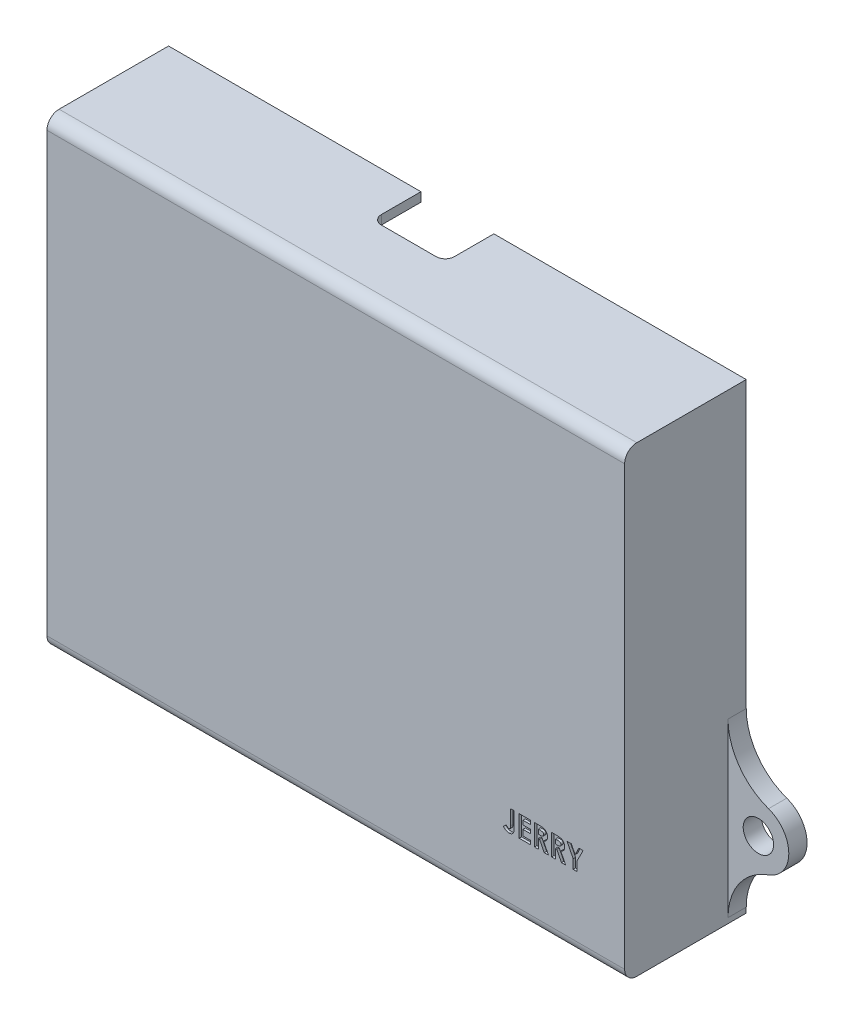
SolidWorks part; units mm, degrees
ref_plane "Front Plane" through (0, 0, 0) normal (0, 0, 1) x (1, 0, 0)
ref_plane "Top Plane" through (0, 0, 0) normal (0, 1, 0) x (1, 0, 0)
ref_plane "Right Plane" through (0, 0, 0) normal (1, 0, 0) x (0, 0, -1)
ref_plane "Plane1" through (-67.462, 80, -13) normal (1, 0, 0) x (0, 0, -1)
sketch "Sketch3" plane through (0, 0, 0) normal (0, 0, 1) x (1, 0, 0)
  line L0 (-47.5, 86) -> (-38, 86) construction
  line L1 (-47.5, 10) -> (-47.5, 10.8579) construction
  line L2 (-47.5, 10) -> (-38, 10) construction
  line L3 (-47.5, 39.1421) -> (-47.5, 86) construction
  line L4 (-47.5, 86) -> (47.5, 86)
  line L5 (-47.5, 10) -> (-47.5, 10.8579)
  line L6 (-47.5, 10) -> (47.5, 10)
  line L7 (-47.5, 39.1421) -> (-47.5, 86)
  line L8 (47.5, 10) -> (47.5, 10.8579) construction
  line L9 (47.5, 10) -> (47.5, 10.8579)
  line L10 (47.5, 39.1421) -> (47.5, 86) construction
  line L11 (47.5, 39.1421) -> (47.5, 86)
  line L12 (0, 10) -> (0, 86) construction
  line L13 (-47.5, 39.1421) -> (-47.5, 10.8579)
  line L14 (-46, 14.5) -> (46, 14.5)
  line L15 (-46, 14.5) -> (-46, 84.5)
  line L16 (-46, 84.5) -> (46, 84.5)
  line L17 (46, 14.5) -> (46, 84.5)
  line L18 (-46, 14.5) -> (46, 84.5) construction
  line L19 (-46, 84.5) -> (46, 14.5) construction
  line L20 (47.5, 39.1421) -> (47.5, 10.8579)
  arc A0 (-47.5, 10.8579) -> (-54.1667, 20.286) centre (-57.5, 10.8579) ccw construction
  arc A1 (-54.1667, 29.714) -> (-54.1667, 20.286) centre (-52.5, 25) ccw construction
  arc A2 (-54.1667, 29.714) -> (-47.5, 39.1421) centre (-57.5, 39.1421) ccw construction
  arc A3 (-47.5, 10.8579) -> (-54.1667, 20.286) centre (-57.5, 10.8579) ccw
  arc A4 (-54.1667, 29.714) -> (-54.1667, 20.286) centre (-52.5, 25) ccw
  arc A5 (-54.1667, 29.714) -> (-47.5, 39.1421) centre (-57.5, 39.1421) ccw
  arc A6 (47.5, 39.1421) -> (54.1667, 29.714) centre (57.5, 39.1421) ccw construction
  arc A7 (54.1667, 20.286) -> (54.1667, 29.714) centre (52.5, 25) ccw construction
  arc A8 (47.5, 39.1421) -> (54.1667, 29.714) centre (57.5, 39.1421) ccw
  arc A9 (54.1667, 20.286) -> (54.1667, 29.714) centre (52.5, 25) ccw
  arc A10 (54.1667, 20.286) -> (47.5, 10.8579) centre (57.5, 10.8579) ccw construction
  arc A11 (54.1667, 20.286) -> (47.5, 10.8579) centre (57.5, 10.8579) ccw
  circle A12 centre (-52.5, 25) radius 2.5
  circle A13 centre (52.5, 25) radius 2.5
  point P1 (0, 49.5)
  circle M7 centre (-52.5, 25) radius 3.85
  circle M8 centre (-41.5, 21) radius 2.35
  circle M9 centre (-41.5, 79) radius 2.35
  line M10 (-47.5, 10) -> (-38, 10)
  line M11 (-38, 10) -> (-38, 86)
  line M12 (-38, 86) -> (-47.5, 86)
  line M13 (-47.5, 86) -> (-47.5, 39.1421)
  arc M14 (-47.5, 39.1421) -> (-54.1667, 29.714) centre (-57.5, 39.1421) cw
  arc M15 (-54.1667, 29.714) -> (-54.1667, 20.286) centre (-52.5, 25) ccw
  arc M16 (-54.1667, 20.286) -> (-47.5, 10.8579) centre (-57.5, 10.8579) cw
  line M17 (-47.5, 10.8579) -> (-47.5, 10)
  dimension "D4" = 5
  dimension "D1" = 1.5
  dimension "D2" = 1.5
  dimension "D3" = 4.5
extrude "Boss-Extrude1" add sketch "Sketch3" along normal blind 3 contours A11 A9 A8 L20 A13 | L13 M14 M15 M16 M7 region at (-47.8, 25, 0) region at (49.0901, 33.1954, 0)
extrude "Boss-Extrude2" add sketch "Sketch3<3>" along normal blind 20 contours L15 L16 L13 L14 M11 M12 M13 M17 M10 | L20 L11 L4 L16 L17 L14 L6 L9 M11 region at (-42.75, 85.2341, 0) region at (4.75, 84.856, 0)
sketch "Sketch3<3>" plane through (0, 0, 0) normal (0, 0, 1) x (1, 0, 0) same geometry as "Sketch3"
extrude "Boss-Extrude3" add sketch "Sketch3<4>" against normal blind 1.5 from surface contours L14 L17 L16 M11 | M9 | L16 L15 L14 M11 M9 M8 | M8 region at (-42.033, 49.467, 0) region at (4, 49.5, 0) region at (-41.5, 21, 0) region at (-41.5, 79, 0) starting at face at (0, 48, 20)
sketch "Sketch3<4>" plane through (0, 0, 0) normal (0, 0, 1) x (1, 0, 0) same geometry as "Sketch3"
fillet "Fillet1" radius 2 4 edges at (0, 14.5, 18.5) (0, 84.5, 18.5) (0, 10, 20) (0, 86, 20)
sketch "Sketch4" plane through (0, 10, 0) normal (0, -1, 0) x (1, 0, 0)
  line L0 (-47.5, 0) -> (47.5, 0) construction
  line L1 (-2.5, 0) -> (-32.5, 0)
  line L2 (-2.5, 0) -> (-2.5, 8)
  line L3 (-2.5, 8) -> (-32.5, 8)
  line L4 (-32.5, 0) -> (-32.5, 8)
  line L5 (47.5, 18) -> (47.5, 0) construction
  line L6 (28.5, 5) -> (34, 5)
  line L7 (28.5, 5) -> (28.5, 0)
  line L8 (28.5, 0) -> (34, 0)
  line L9 (34, 5) -> (34, 0)
  circle A0 centre (31.25, 5) radius 2.75
  point P13 (28.3726, 4.7868)
  line M9 (-47.5, 0) -> (47.5, 0)
  dimension "D4" = 5.5
  dimension "D1" = 8
  dimension "D2" = 30
  dimension "D3" = 15
  dimension "D5" = 5
  dimension "D6" = 13.5
extrude "Cut-Extrude1" cut sketch "Sketch4" against normal up to surface (4.5 mm away) contours L4 L2 L3 M9 | L6 A0 | L6 A0 | A0 L7 L9 M9 region at (-17.5, 10, 4) region at (31.25, 10, 1.4864) region at (31.25, 10, 6.1671) region at (31.25, 10, 3.8329) up to face at (0, 14.5, 8.25)
sketch "Sketch5" plane through (-47.5, 0, 0) normal (-1, 0, 0) x (0, 0, 1)
  line L0 (14.5, 69) -> (14.5, 63) construction
  line L1 (18.5, 69) -> (18.5, 63)
  line L2 (10.5, 69) -> (10.5, 63)
  line L3 (18, 86) -> (0, 86) construction
  line L4 (0, 86) -> (0, 39.1421) construction
  arc A0 (18.5, 69) -> (10.5, 69) centre (14.5, 69) ccw
  arc A1 (10.5, 63) -> (18.5, 63) centre (14.5, 63) ccw
  point P2 (14.5, 66)
  point P7 (14.5, 73)
  point P8 (14.5, 59)
  dimension "D1" = 8
  dimension "D2" = 14
  dimension "D3" = 20
  dimension "D4" = 14.5
extrude "Cut-Extrude2" cut sketch "Sketch5" against normal up to surface (1.5 mm away) contours L2 A1 L1 A0 region at (-47.5, 66, 14.5) up to face at (-46, 49.5, 11.8047)
sketch "Sketch6" plane through (0, 86, 0) normal (0, 1, 0) x (1, 0, 0)
  line L0 (47.5, 0) -> (-47.5, 0) construction
  line L1 (-6, -8) -> (6, -8)
  line L2 (-6, -8) -> (-6, 0)
  line L3 (-6, 0) -> (6, 0)
  line L4 (6, -8) -> (6, 0)
  line L5 (-6, -8) -> (6, 0) construction
  line L6 (-6, 0) -> (6, -8) construction
  line L7 (0, -4) -> (0, 0) construction
  point P0 (0, -4)
  point P9 (0, 0)
  point P10 (11.0623, -6.7225)
  line M7 (47.5, 0) -> (-47.5, 0)
  dimension "D1" = 12
  dimension "D2" = 8
extrude "Cut-Extrude3" cut sketch "Sketch6" against normal up to surface (1.5 mm away) contours L1 L4 L2 M7 region at (0, 86, 4) up to face at (0, 84.5, 8.25)
fillet "Fillet2" radius 1.5 4 edges at (-6, 85.25, 8) (6, 85.25, 8) (-2.5, 12.25, 8) (-32.5, 12.25, 8)
sketch "Sketch7" plane through (0, 0, 20) normal (0, 0, 1) x (1, 0, 0)
  line L0 (-47.5, 84) -> (47.5, 12) construction
  line L1 (47.5, 84) -> (47.5, 12) construction
  line L2 (-47.5, 12) -> (47.5, 12) construction
  line L3 (24.3056, 22) -> (44.3056, 22) construction
  line L4 (28.719, 25.5) -> (29.3472, 25.5)
  line L5 (29.3472, 25.5) -> (29.3472, 23.1765)
  line L6 (27.5524, 22.4059) -> (28.0277, 22.8456)
  line L7 (28.719, 23.0306) -> (28.719, 25.5)
  line L8 (30.1549, 25.5) -> (32.0395, 25.5)
  line L9 (32.0395, 25.5) -> (32.0395, 24.8718)
  line L10 (32.0395, 24.8718) -> (30.7831, 24.8718)
  line L11 (30.7831, 24.8718) -> (30.7831, 24.1987)
  line L12 (30.7831, 24.1987) -> (32.0395, 24.1987)
  line L13 (32.0395, 24.1987) -> (32.0395, 23.5705)
  line L14 (32.0395, 23.5705) -> (30.7831, 23.5705)
  line L15 (30.7831, 23.5705) -> (30.7831, 22.6282)
  line L16 (30.7831, 22.6282) -> (32.0395, 22.6282)
  line L17 (32.0395, 22.6282) -> (32.0395, 22)
  line L18 (32.0395, 22) -> (30.1549, 22)
  line L19 (30.1549, 22) -> (30.1549, 25.5)
  line L20 (32.6677, 25.5) -> (33.3997, 25.5)
  line L21 (34.1709, 23.5972) -> (34.9786, 22)
  line L22 (34.9786, 22) -> (34.2803, 22)
  line L23 (34.2803, 22) -> (33.5091, 23.5256)
  line L24 (33.5091, 23.5256) -> (33.2959, 23.5256)
  line L25 (33.2959, 23.5256) -> (33.2959, 22)
  line L26 (33.2959, 22) -> (32.6677, 22)
  line L27 (32.6677, 22) -> (32.6677, 25.5)
  line L28 (33.2959, 24.1538) -> (33.5406, 24.1538)
  line L29 (33.5098, 24.8718) -> (33.2959, 24.8718)
  line L30 (33.2959, 24.8718) -> (33.2959, 24.1538)
  line L31 (35.4947, 25.5) -> (36.2266, 25.5)
  line L32 (36.9979, 23.5972) -> (37.8056, 22)
  line L33 (37.8056, 22) -> (37.1072, 22)
  line L34 (37.1072, 22) -> (36.336, 23.5256)
  line L35 (36.336, 23.5256) -> (36.1229, 23.5256)
  line L36 (36.1229, 23.5256) -> (36.1229, 22)
  line L37 (36.1229, 22) -> (35.4947, 22)
  line L38 (35.4947, 22) -> (35.4947, 25.5)
  line L39 (36.1229, 24.1538) -> (36.3676, 24.1538)
  line L40 (36.3367, 24.8718) -> (36.1229, 24.8718)
  line L41 (36.1229, 24.8718) -> (36.1229, 24.1538)
  line L42 (38.0299, 25.5) -> (38.7289, 25.5)
  line L43 (38.7289, 25.5) -> (39.3536, 24.2716)
  line L44 (39.3536, 24.2716) -> (39.9797, 25.5)
  line L45 (39.9797, 25.5) -> (40.6774, 25.5)
  line L46 (40.6774, 25.5) -> (39.6677, 23.5158)
  line L47 (39.6677, 23.5158) -> (39.6677, 22)
  line L48 (39.6677, 22) -> (39.0395, 22)
  line L49 (39.0395, 22) -> (39.0395, 23.5158)
  line L50 (39.0395, 23.5158) -> (38.0299, 25.5)
  spline S0 degree 3 poles (29.3472, 23.1765) (29.3475, 23.0909) (29.3445, 22.9677) (29.3361, 22.8104) (29.3274, 22.7079) (29.3146, 22.6158) (29.3001, 22.5339) (29.284, 22.4619) (29.2569, 22.3812) (29.2148, 22.292) (29.1513, 22.1956) (29.0723, 22.1118) (28.9812, 22.039) (28.8774, 21.9815) (28.7214, 21.9243) (28.5945, 21.9107) (28.5087, 21.9103) knots 0 0 0 0 0.147218 0.212059 0.270999 0.324171 0.37197 0.414105 0.450981 0.518077 0.58332 0.648756 0.71545 0.783135 0.852085 1 1 1 1
  spline S1 degree 3 poles (28.5087, 21.9103) (28.4177, 21.9101) (28.2823, 21.925) (28.1098, 21.977) (27.9873, 22.0326) (27.8691, 22.1023) (27.7162, 22.22) (27.614, 22.327) (27.5524, 22.4059) knots 0 0 0 0 0.244326 0.363092 0.482806 0.604691 0.731012 1 1 1 1
  spline S2 degree 3 poles (28.0277, 22.8456) (28.0735, 22.7923) (28.141, 22.7207) (28.2327, 22.6409) (28.2924, 22.6011) (28.3487, 22.5731) (28.4191, 22.5467) (28.4739, 22.5393) (28.5094, 22.5385) knots 0 0 0 0 0.357766 0.499586 0.618045 0.721796 0.819272 1 1 1 1
  spline S3 degree 3 poles (28.5094, 22.5385) (28.5415, 22.5375) (28.5895, 22.5491) (28.6402, 22.5891) (28.6649, 22.6229) (28.6805, 22.6574) (28.6904, 22.6907) (28.6997, 22.7307) (28.7071, 22.7774) (28.7127, 22.8312) (28.7168, 22.9163) (28.7199, 22.9836) (28.719, 23.0306) knots 0 0 0 0 0.160852 0.236744 0.319648 0.367326 0.42621 0.493524 0.573025 0.662506 0.764543 1 1 1 1
  spline S4 degree 3 poles (33.3997, 25.5) (33.4928, 25.5005) (33.627, 25.4972) (33.7986, 25.487) (33.9111, 25.476) (34.0129, 25.4613) (34.1039, 25.444) (34.1843, 25.4243) (34.2547, 25.3997) (34.3182, 25.372) (34.3774, 25.3402) (34.4336, 25.3046) (34.4864, 25.2642) (34.5363, 25.2199) (34.5834, 25.1716) (34.6269, 25.1188) (34.6668, 25.0619) (34.703, 25.0021) (34.7351, 24.9392) (34.7612, 24.8732) (34.7843, 24.8051) (34.8008, 24.7339) (34.8166, 24.6342) (34.8226, 24.5577) (34.8216, 24.5058) knots 0 0 0 0 0.140186 0.202277 0.258895 0.310483 0.357095 0.398514 0.435038 0.469251 0.502805 0.53621 0.569379 0.602801 0.636666 0.670929 0.705803 0.741189 0.776304 0.812004 0.847969 0.884522 0.921974 1 1 1 1
  spline S5 degree 3 poles (34.8216, 24.5058) (34.8207, 24.4517) (34.8174, 24.3719) (34.8004, 24.2686) (34.7816, 24.1963) (34.76, 24.1266) (34.7312, 24.0611) (34.6987, 23.9986) (34.6601, 23.9401) (34.6178, 23.8843) (34.5686, 23.8333) (34.5156, 23.7844) (34.456, 23.7406) (34.3923, 23.699) (34.2985, 23.6475) (34.2232, 23.6156) (34.1709, 23.5972) knots 0 0 0 0 0.134789 0.198536 0.260386 0.320962 0.379904 0.438503 0.496154 0.554265 0.612749 0.672513 0.733646 0.79679 0.861936 1 1 1 1
  spline S6 degree 3 poles (33.5406, 24.1538) (33.5979, 24.1547) (33.6804, 24.155) (33.785, 24.165) (33.8526, 24.1741) (33.9133, 24.1847) (33.9665, 24.1997) (34.0132, 24.2159) (34.0526, 24.236) (34.0863, 24.2588) (34.1154, 24.2847) (34.1395, 24.3147) (34.1593, 24.348) (34.1747, 24.3848) (34.1903, 24.44) (34.1932, 24.4842) (34.1934, 24.5142) knots 0 0 0 0 0.202086 0.290685 0.370553 0.44267 0.507675 0.565573 0.616455 0.663331 0.708862 0.753412 0.798515 0.845064 0.893873 1 1 1 1
  spline S7 degree 3 poles (34.1934, 24.5142) (34.1938, 24.5506) (34.1852, 24.6047) (34.1552, 24.6702) (34.125, 24.7146) (34.0868, 24.7536) (34.043, 24.7879) (33.9926, 24.8151) (33.946, 24.833) (33.9035, 24.8437) (33.8653, 24.8517) (33.8209, 24.8573) (33.7705, 24.8633) (33.7141, 24.8672) (33.6265, 24.8712) (33.5577, 24.8713) (33.5098, 24.8718) knots 0 0 0 0 0.125262 0.185414 0.246807 0.309422 0.372533 0.437733 0.50575 0.544013 0.58837 0.640389 0.697897 0.763272 0.834979 1 1 1 1
  spline S8 degree 3 poles (36.2266, 25.5) (36.3197, 25.5005) (36.4539, 25.4972) (36.6255, 25.487) (36.738, 25.476) (36.8398, 25.4613) (36.9308, 25.444) (37.0112, 25.4243) (37.0816, 25.3997) (37.1451, 25.372) (37.2043, 25.3402) (37.2605, 25.3046) (37.3133, 25.2642) (37.3632, 25.2199) (37.4103, 25.1716) (37.4539, 25.1188) (37.4937, 25.0619) (37.53, 25.0021) (37.562, 24.9392) (37.5881, 24.8732) (37.6112, 24.8051) (37.6278, 24.7339) (37.6435, 24.6342) (37.6495, 24.5577) (37.6485, 24.5058) knots 0 0 0 0 0.140186 0.202277 0.258895 0.310483 0.357095 0.398514 0.435038 0.469251 0.502805 0.53621 0.569379 0.602801 0.636666 0.670929 0.705803 0.741189 0.776304 0.812004 0.847969 0.884522 0.921974 1 1 1 1
  spline S9 degree 3 poles (37.6485, 24.5058) (37.6477, 24.4517) (37.6443, 24.3719) (37.6274, 24.2686) (37.6085, 24.1963) (37.5869, 24.1266) (37.5581, 24.0611) (37.5256, 23.9986) (37.4871, 23.9401) (37.4447, 23.8843) (37.3955, 23.8333) (37.3426, 23.7844) (37.2829, 23.7406) (37.2192, 23.699) (37.1254, 23.6475) (37.0501, 23.6156) (36.9979, 23.5972) knots 0 0 0 0 0.134789 0.198536 0.260386 0.320962 0.379904 0.438503 0.496154 0.554265 0.612749 0.672513 0.733646 0.79679 0.861936 1 1 1 1
  spline S10 degree 3 poles (36.3676, 24.1538) (36.4248, 24.1547) (36.5073, 24.155) (36.612, 24.165) (36.6795, 24.1741) (36.7402, 24.1847) (36.7935, 24.1997) (36.8401, 24.2159) (36.8795, 24.236) (36.9133, 24.2588) (36.9424, 24.2847) (36.9664, 24.3147) (36.9862, 24.348) (37.0017, 24.3848) (37.0172, 24.44) (37.0201, 24.4842) (37.0203, 24.5142) knots 0 0 0 0 0.202086 0.290685 0.370553 0.44267 0.507675 0.565573 0.616455 0.663331 0.708862 0.753412 0.798515 0.845064 0.893873 1 1 1 1
  spline S11 degree 3 poles (37.0203, 24.5142) (37.0207, 24.5506) (37.0122, 24.6047) (36.9822, 24.6702) (36.9519, 24.7146) (36.9137, 24.7536) (36.8699, 24.7879) (36.8195, 24.8151) (36.7729, 24.833) (36.7305, 24.8437) (36.6922, 24.8517) (36.6478, 24.8573) (36.5974, 24.8633) (36.541, 24.8672) (36.4534, 24.8712) (36.3846, 24.8713) (36.3367, 24.8718) knots 0 0 0 0 0.125262 0.185414 0.246807 0.309422 0.372533 0.437733 0.50575 0.544013 0.58837 0.640389 0.697897 0.763272 0.834979 1 1 1 1
  point P10 (34.3056, 22)
  dimension "D1" = 10
  dimension "D2" = 20
extrude "Cut-Extrude4" cut sketch "Sketch7" against normal blind 0.4 contours S3 S2 L6 S1 S0 L5 L4 L7 | L19 L18 L17 L16 L15 L14 L13 L12 L11 L10 L9 L8 | S5 S4 L20 L27 L26 L25 L24 L23 L22 L21 S7 S6 L28 L30 L29 | S9 S8 L31 L38 L37 L36 L35 L34 L33 L32 S11 S10 L39 L41 L40 | L50 L49 L48 L47 L46 L45 L44 L43 L42 region at (28.8213, 23.4491, 20) region at (30.9576, 23.7733, 20) region at (33.6461, 23.8405, 20) region at (36.473, 23.8405, 20) region at (39.3535, 24.0852, 20)
